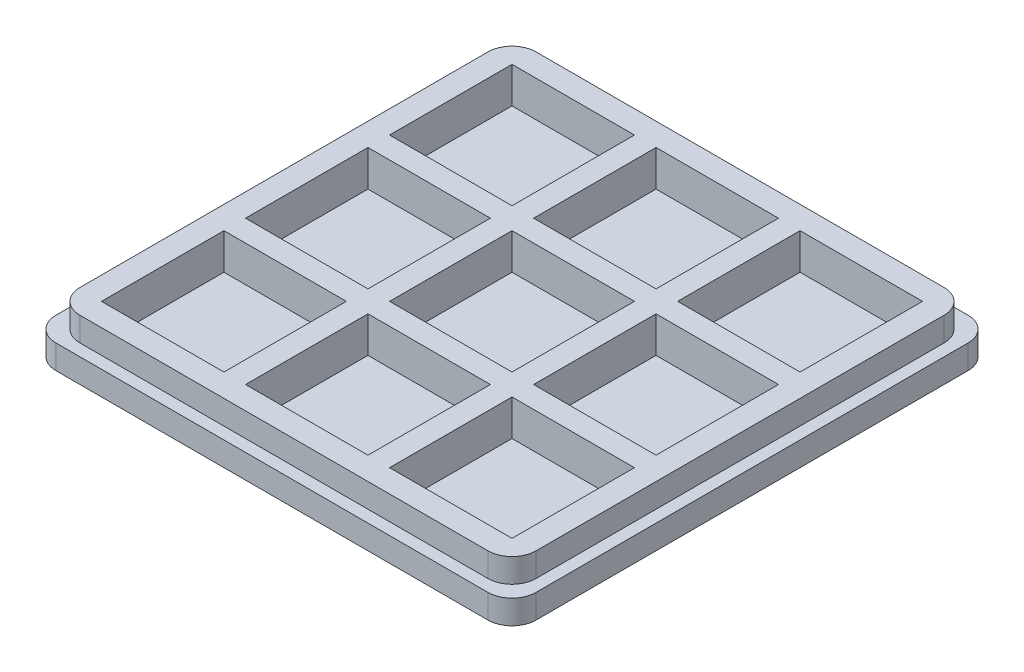
SolidWorks part; units mm, degrees
ref_plane "Front" through (0, 0, 0) normal (0, 0, 1) x (1, 0, 0)
ref_plane "Top" through (0, 0, 0) normal (0, 1, 0) x (1, 0, 0)
ref_plane "Right" through (0, 0, 0) normal (1, 0, 0) x (0, 0, -1)
sketch "草图1" plane through (0, 0, 0) normal (0, 1, 0) x (1, 0, 0)
  line L0 (25.5, 85.5) -> (25.5, 34.5)
  line L1 (-100, 100) -> (100, 100)
  line L2 (-100, 100) -> (-100, -100)
  line L3 (-100, -100) -> (100, -100)
  line L4 (100, 100) -> (100, -100)
  line L5 (-100, 100) -> (100, -100) construction
  line L6 (-100, -100) -> (100, 100) construction
  line L7 (-85.5, 85.5) -> (-34.5, 85.5)
  line L8 (-85.5, 85.5) -> (-85.5, 34.5)
  line L9 (-85.5, 34.5) -> (-34.5, 34.5)
  line L10 (-34.5, 85.5) -> (-34.5, 34.5)
  line L11 (-85.5, 85.5) -> (-34.5, 34.5) construction
  line L12 (-85.5, 34.5) -> (-34.5, 85.5) construction
  line L13 (-25.5, 85.5) -> (25.5, 85.5)
  line L14 (-25.5, 34.5) -> (25.5, 34.5)
  line L15 (-25.5, 85.5) -> (-25.5, 34.5)
  line L16 (85.5, 85.5) -> (85.5, 34.5)
  line L17 (34.5, 85.5) -> (85.5, 85.5)
  line L18 (34.5, 34.5) -> (85.5, 34.5)
  line L19 (34.5, 85.5) -> (34.5, 34.5)
  line L20 (25.5, 25.5) -> (25.5, -25.5)
  line L21 (-25.5, 25.5) -> (25.5, 25.5)
  line L22 (-25.5, -25.5) -> (25.5, -25.5)
  line L23 (-25.5, 25.5) -> (-25.5, -25.5)
  line L24 (85.5, 25.5) -> (85.5, -25.5)
  line L25 (34.5, 25.5) -> (85.5, 25.5)
  line L26 (34.5, -25.5) -> (85.5, -25.5)
  line L27 (34.5, 25.5) -> (34.5, -25.5)
  line L28 (25.5, -34.5) -> (25.5, -85.5)
  line L29 (-25.5, -34.5) -> (25.5, -34.5)
  line L30 (-25.5, -85.5) -> (25.5, -85.5)
  line L31 (-25.5, -34.5) -> (-25.5, -85.5)
  line L32 (85.5, -34.5) -> (85.5, -85.5)
  line L33 (34.5, -34.5) -> (85.5, -34.5)
  line L34 (34.5, -85.5) -> (85.5, -85.5)
  line L35 (34.5, -34.5) -> (34.5, -85.5)
  line L36 (-34.5, 25.5) -> (-34.5, -25.5)
  line L37 (-85.5, 25.5) -> (-34.5, 25.5)
  line L38 (-85.5, -25.5) -> (-34.5, -25.5)
  line L39 (-85.5, 25.5) -> (-85.5, -25.5)
  line L40 (-34.5, -34.5) -> (-34.5, -85.5)
  line L41 (-85.5, -34.5) -> (-34.5, -34.5)
  line L42 (-85.5, -85.5) -> (-34.5, -85.5)
  line L43 (-85.5, -34.5) -> (-85.5, -85.5)
  point P0 (0, 0)
  point P6 (-65.2174, 62.1852)
  dimension "D1" = 200
  dimension "D2" = 200
  dimension "D3" = 51
  dimension "D4" = 51
  dimension "D5" = 14.5
  dimension "D6" = 14.5
  dimension "D7" = 3
  dimension "D8" = 3
extrude "凸台-拉伸1" add sketch "草图1" along normal blind 20
extrude "凸台-拉伸2" add sketch "草图1<2>" along normal blind 5 contours L1 L4 L3 L2
sketch "草图1<2>" plane through (0, 0, 0) normal (0, 1, 0) x (1, 0, 0) same geometry as "草图1"
sketch "草图2" plane through (0, 20, 0) normal (0, 1, 0) x (1, 0, 0)
  line L0 (-95, 95) -> (95, 95)
  line L1 (95, 95) -> (95, -95)
  line L2 (95, -95) -> (-95, -95)
  line L3 (-95, -95) -> (-95, 95)
  line L4 (100, 100) -> (-100, 100) construction
  line L5 (-100, 100) -> (-100, -100) construction
  line L6 (-100, -100) -> (100, -100) construction
  line L7 (100, -100) -> (100, 100) construction
  line L9 (-100, 100) -> (100, 100)
  line L10 (-100, 100) -> (-100, -100)
  line L11 (-100, -100) -> (100, -100)
  line L12 (100, 100) -> (100, -100)
  line L13 (-100, 100) -> (100, -100) construction
  line L14 (-100, -100) -> (100, 100) construction
  point P12 (0, 0)
  dimension "D1" = 5
  dimension "D2" = 5
  dimension "D3" = 5
  dimension "D4" = 5
extrude "切除-拉伸1" cut sketch "草图2" against normal blind 10
fillet "圆角1" radius 10 8 edges at (-95, 15, 95) (-100, 5, 100) (95, 15, 95) (100, 5, 100) (95, 15, -95) (100, 5, -100) (-95, 15, -95) (-100, 5, -100)
